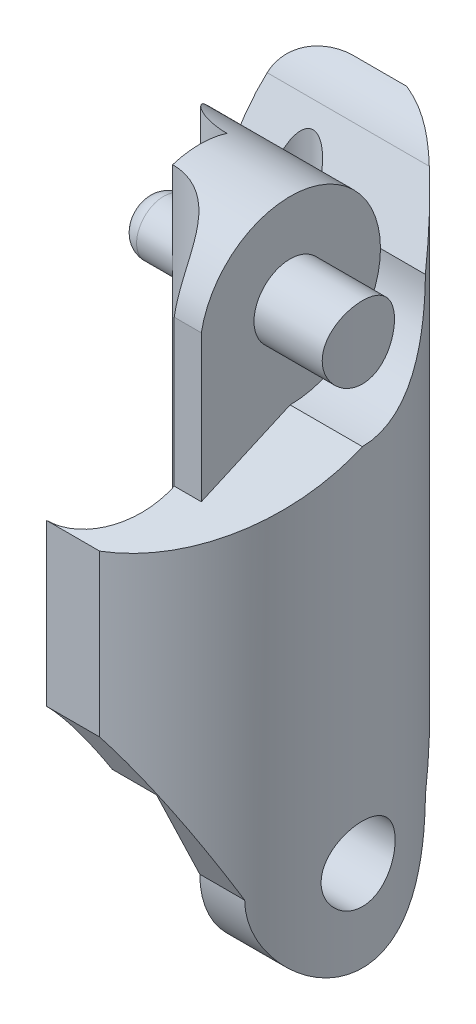
SolidWorks part; units mm, degrees
ref_plane "Front Plane" through (0, 0, 0) normal (0, 0, 1) x (1, 0, 0)
ref_plane "Top Plane" through (0, 0, 0) normal (0, 1, 0) x (1, 0, 0)
ref_plane "Right Plane" through (0, 0, 0) normal (1, 0, 0) x (0, 0, -1)
sketch "Sketch1" plane through (0, 0, 0) normal (0, 1, 0) x (1, 0, 0)
  line L0 (-2.958, 8.5) -> (2.958, 8.5)
  line L1 (-2.958, -8.5) -> (2.958, -8.5)
  arc A0 (-2.958, 8.5) -> (-2.958, -8.5) centre (0, 0) ccw
  arc A1 (2.958, 8.5) -> (2.958, -8.5) centre (0, 0) cw
  point P9 (-9, 0)
  point P10 (9, 0)
  dimension "D1" = 18
  dimension "D2" = 17
extrude "Boss-Extrude1" add sketch "Sketch1" along normal blind 35
sketch "Sketch2" plane through (0, 0, 0) normal (0, -1, 0) x (1, 0, 0)
  circle A0 centre (0, -5) radius 1.27
  circle A1 centre (0, 5) radius 1.27
  dimension "D1" = 2.54
  dimension "D2" = 5
  dimension "D3" = 5
extrude "Cut-Extrude1" cut sketch "Sketch2" against normal blind 35
sketch "Sketch3" plane through (0, 0, -8.5) normal (0, 0, -1) x (-1, 0, 0)
  line L0 (5, 0) -> (5, 10)
  line L1 (5, 10) -> (-5, 10)
  line L2 (-5, 10) -> (-5, 0)
  line L3 (5, 0) -> (-5, 0)
  line L4 (-2.958, 0) -> (2.958, 0) construction
  point P10 (0, 0)
  dimension "D1" = 10
  dimension "D2" = 10
extrude "Cut-Extrude2" cut sketch "Sketch3" against normal up to surface (17 mm away) up to face at (0, 17.5, 8.5)
sketch "Sketch4" plane through (5, 0, 0) normal (-1, 0, 0) x (0, 0, 1)
  line L0 (-7.4833, 10) -> (-5, 5)
  line L1 (8.5, 12.3086) -> (5, 5)
  line L2 (7.4833, 0) -> (-7.4833, 0) construction
  line L3 (-7.4833, 10) -> (-9.8579, -1.8222)
  line L4 (-9.8579, -1.8222) -> (9.8579, -1.8222)
  line L6 (8.5, 35) -> (8.5, 10) construction
  line L7 (9.8579, -1.8222) -> (8.5, 12.3086)
  arc A0 (-5, 5) -> (5, 5) centre (0, 5) ccw
  circle A1 centre (0, 5) radius 2.05
  point P7 (0, 0)
  dimension "D1" = 4.1
  dimension "D2" = 5
  dimension "D3" = 12.0584
  dimension "D4" = 37.769
extrude "Cut-Extrude3" cut sketch "Sketch4" against normal mid plane 35
ref_plane "Plane1" through (-2.958, 0, 0) normal (-1, 0, 0) x (0, 0, 1)
sketch "Sketch6" plane through (-2.958, 0, 0) normal (-1, 0, 0) x (0, 0, 1)
  line L0 (8.5, 21.2199) -> (0, 25)
  line L1 (8.5, 35) -> (8.5, 12.3086) construction
  line L2 (-5, 30) -> (-6.7559, 33.5353)
  line L3 (8.5, 35) -> (-8.5, 35) construction
  line L4 (8.5, 21.2199) -> (17.803, 42.886)
  line L6 (-7.4833, 10) -> (-5, 5) construction
  line L7 (-8.5, 35) -> (17.803, 42.886)
  arc A0 (0, 25) -> (-5, 30) centre (0, 30) cw
  circle A1 centre (0, 30) radius 2
  arc A2 (-6.7559, 33.5353) -> (-8.5, 35) centre (-9.3069, 32.2683) ccw
  dimension "D1" = 5
  dimension "D3" = 4
  dimension "D2" = 5
  dimension "D4" = 8.5
extrude "Cut-Extrude5" cut sketch "Sketch6" against normal blind 9.6 from surface starting at face at (5, 7.05, 0)
sketch "Sketch7" plane through (5, 0, 0) normal (1, 0, 0) x (0, 0, -1)
  line L0 (5, 30) -> (6.7559, 33.5353)
  line L2 (-8.3419, 47.5367) -> (-13.1682, 33.5285)
  line L3 (-7.4833, 35) -> (7.4833, 35) construction
  line L4 (-4.9155, 30.9155) -> (-4.9155, 22.814)
  line L5 (-7.4833, 21.6721) -> (0, 25) construction
  line L6 (-4.9155, 22.814) -> (-10.0468, 20.532)
  line L7 (-10.0468, 20.532) -> (-13.1682, 33.5285)
  line L8 (6.7559, 33.5353) -> (5, 30) construction
  line L9 (8.5, 35) -> (-8.3419, 47.5367)
  arc A0 (5, 30) -> (-4.9155, 30.9155) centre (0, 30) ccw
  arc A1 (6.7559, 33.5353) -> (8.5, 35) centre (9.3069, 32.2683) cw
  arc A2 (7.4833, 34.4564) -> (6.7559, 33.5353) centre (9.3069, 32.2683) ccw construction
  dimension "D1" = 5
fillet "Fillet3" radius 1 2 edges at (0, 10, -3.73) (0, 10, 6.27)
extrude "Cut-Extrude6" cut sketch "Sketch6<3>" along normal blind 6.604 from surface starting at face at (-5, 2.95, 0)
sketch "Sketch6<3>" plane through (-2.958, 0, 0) normal (-1, 0, 0) x (0, 0, 1) same geometry as "Sketch6"
extrude "Cut-Extrude7" cut sketch "Sketch7" against normal blind 14.986
sketch "Sketch8" plane through (0, 10, 0) normal (0, -1, 0) x (1, 0, 0)
  line L0 (0, 1.5) -> (0, -1.5)
  line L1 (-2.958, -8.5) -> (2.958, -8.5) construction
  line L2 (2.958, 8.5) -> (-2.958, 8.5) construction
  line L3 (0, 8.5) -> (-4.7901, 15.219)
  line L4 (-4.7901, 15.219) -> (-17.8556, -9.7177)
  line L5 (-17.8556, -9.7177) -> (-4.7901, -16.0136)
  line L6 (-4.7901, -16.0136) -> (0, -8.5)
  arc A0 (0, -1.5) -> (0, -8.5) centre (0, -5) ccw
  arc A1 (0, 1.5) -> (0, 8.5) centre (0, 5) ccw
  circle A2 centre (0, 5) radius 2.27 construction
  circle A3 centre (0, -5) radius 2.27 construction
extrude "Cut-Extrude8" cut sketch "Sketch8" against normal mid plane 62.992
sketch "Sketch9" plane through (0, 0, 0) normal (-1, 0, 0) x (0, 0, 1)
  line L0 (7.3945, 10) -> (-7.4833, 10) construction
  circle A0 centre (0, 16) radius 1.5
  dimension "D2" = 3
  dimension "D1" = 6
extrude "Cut-Extrude9" cut sketch "Sketch9" against normal blind 8.382
sketch "Sketch11" plane through (0, 0, 0) normal (-1, 0, 0) x (0, 0, 1)
  circle A0 centre (0, 16) radius 2
  dimension "D1" = 4
extrude "Cut-Extrude10" cut sketch "Sketch11" against normal mid plane 6.2
sketch "Sketch12" plane through (0, 0, 0) normal (-1, 0, 0) x (0, 0, 1)
  line L0 (0, 18) -> (0, 19.5)
  line L1 (0, 14) -> (0, 12.5)
  arc A0 (1.5, 17.3229) -> (-1.5, 17.3229) centre (0, 16) ccw construction
  arc A1 (-1.5, 14.6771) -> (1.5, 14.6771) centre (0, 16) ccw construction
  arc A2 (0, 19.5) -> (0, 12.5) centre (0, 16) cw
  arc A3 (1.5, 14.6771) -> (1.5, 17.3229) centre (0, 16) ccw construction
  arc A4 (0, 18) -> (0, 14) centre (0, 16) cw
  point P17 (0, 14)
  dimension "D1" = 1.5
extrude "Boss-Extrude2" add sketch "Sketch12" against normal blind 3.862
sketch "Sketch13" plane through (0, 0, 0) normal (-1, 0, 0) x (0, 0, 1)
  line L0 (1.5, 34.7697) -> (1.5, 19.1623) construction
  circle A0 centre (0, 30) radius 1.5
  circle A1 centre (0, 30) radius 2 construction
extrude "Boss-Extrude3" add sketch "Sketch13" along normal blind 3
fillet "Fillet4" radius 1 1 edges at (-3, 30, 1.5)
